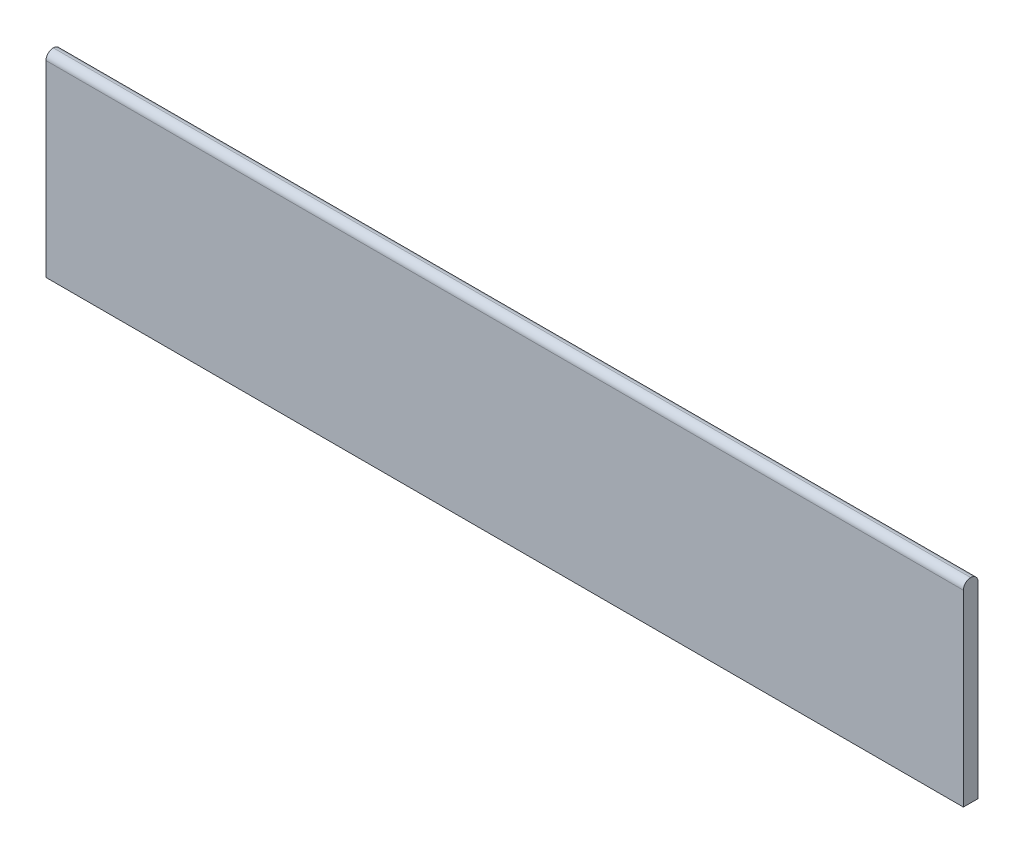
SolidWorks part; units mm, degrees
ref_plane "Plan de face" through (0, 0, 0) normal (0, 0, 1) x (1, 0, 0)
ref_plane "Plan de dessus" through (0, 0, 0) normal (0, 1, 0) x (1, 0, 0)
ref_plane "Plan de droite" through (0, 0, 0) normal (1, 0, 0) x (0, 0, -1)
sketch "Esquisse1" plane through (0, 0, 0) normal (0, 0, 1) x (1, 0, 0)
  line L1 (0, 0) -> (188, 0)
  line L2 (0, 0) -> (0, 40)
  line L3 (0, 40) -> (188, 40)
  line L4 (188, 0) -> (188, 40)
  dimension "D1" = 188
  dimension "D2" = 40
extrude "Boss.-Extru.1" add sketch "Esquisse1" along normal blind 3
fillet "Congé1" radius 1.5 1 edges at (94, 40, 3)
fillet "Congé3" radius 1.5 1 edges at (94, 40, 0)
